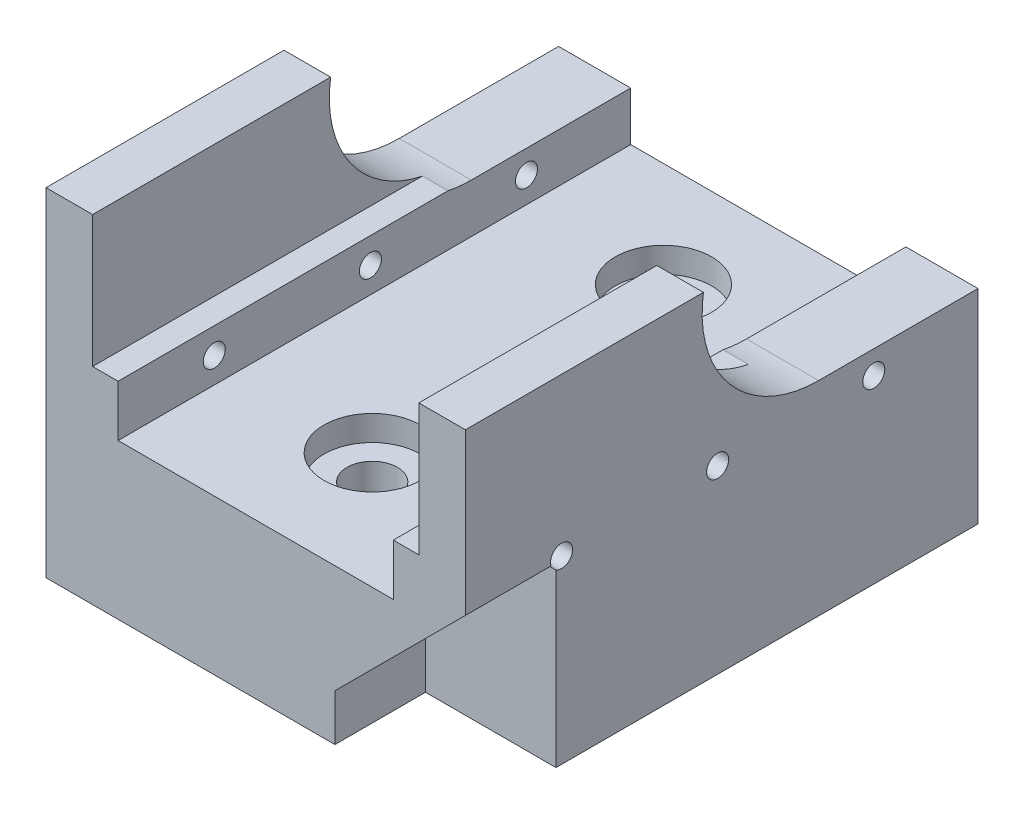
SolidWorks part; units mm, degrees
material "PLA"
ref_plane "Front Plane" through (0, 0, 0) normal (0, 0, 1) x (1, 0, 0)
ref_plane "Top Plane" through (0, 0, 0) normal (0, 1, 0) x (1, 0, 0)
ref_plane "Right Plane" through (0, 0, 0) normal (1, 0, 0) x (0, 0, -1)
sketch "Sketch1" plane through (0, 0, 0) normal (0, 1, 0) x (1, 0, 0)
  line L0 (-22.86, 30.48) -> (22.86, 30.48)
  line L6 (-22.86, 30.48) -> (-22.86, -30.48)
  line L8 (22.86, 30.48) -> (22.86, -30.48)
  line L9 (-22.86, -30.48) -> (22.86, -30.48)
  point P1 (-22.86, 0)
  point P7 (22.86, 0)
  dimension "D3" = 30.48
  dimension "D2" = 45.72
  dimension "D1" = 60.96
  dimension "D4" = 22.86
extrude "Boss-Extrude1" add sketch "Sketch1" along normal blind 6.35
sketch "Sketch2" plane through (0, 6.35, 0) normal (0, 1, 0) x (1, 0, 0)
  line L9 (-22.86, -30.48) -> (22.86, -30.48) construction
  line L10 (-22.86, 30.48) -> (-15, 30.48)
  line L11 (-22.86, 30.48) -> (-22.86, -30.48)
  line L12 (-22.86, -30.48) -> (-15, -30.48)
  line L13 (-15, 30.48) -> (-15, -30.48)
  line L14 (22.86, 30.48) -> (-22.86, 30.48) construction
  line L15 (15, 30.48) -> (22.86, 30.48)
  line L16 (15, 30.48) -> (15, -30.48)
  line L17 (15, -30.48) -> (22.86, -30.48)
  line L18 (22.86, 30.48) -> (22.86, -30.48)
  dimension "D1" = 7.86
  dimension "D2" = 7.86
extrude "Boss-Extrude2" add sketch "Sketch2" along normal blind 20.955
hole_wizard "M2 Clearance Hole2" positions "Sketch6" profile "Sketch7" hole size "M2" standard "ANSI Metric"
sketch "Sketch6" plane through (22.86, 0, 0) normal (1, 0, 0) x (0, 0, -1)
  line L0 (-30.48, 27.305) -> (-30.48, 0) construction
  line L1 (-30.48, 0) -> (30.48, 0) construction
  point P0 (-14.9172, 10.16)
  dimension "D1" = 15.5628
  dimension "D2" = 10.16
sketch "Sketch7" plane through (22.86, 10.16, 14.9172) normal (0, 1, 0) x (0, 0, -1)
  line L0 (0, 0) -> (0, 46.441)
  line L1 (0, 46.441) -> (1.2, 45.72)
  line L2 (1.2, 45.72) -> (1.2, 0)
  line L5 (1.2, 0) -> (0, 0)
  line L10 (0, 46.441) -> (-1.2, 45.72) construction
  line L11 (0, -6.35) -> (0, 107.95) construction
  dimension "Hole Dia." = 2.4
  dimension "Hole Depth" = 45.72
  dimension "Drill Angle" = 118
pattern_linear "LPattern1" count 3 spacing 17.018 along (0, 0, -1) of "M2 Clearance Hole2"
extrude "Boss-Extrude3" add sketch "Sketch1<3>" against normal blind 2.54
sketch "Sketch1<3>" plane through (0, 0, 0) normal (0, 1, 0) x (1, 0, 0) same geometry as "Sketch1"
sketch "Sketch8" plane through (-22.86, 0, 0) normal (-1, 0, 0) x (0, 0, 1)
  line L0 (-30.48, 27.305) -> (-30.48, -2.54) construction
  line L1 (-30.48, -2.54) -> (-14.605, -2.54)
  line L2 (-30.48, -2.54) -> (-30.48, 3.81)
  line L3 (-30.48, 3.81) -> (-14.605, 3.81)
  line L4 (-14.605, -2.54) -> (-14.605, 3.81)
  line L5 (-30.48, -2.54) -> (30.48, -2.54) construction
  dimension "D1" = 15.875
  dimension "D2" = 6.35
sketch "Sketch11" plane through (15, 0, 0) normal (-1, 0, 0) x (0, 0, 1)
  line L0 (30.48, 27.305) -> (30.48, 6.35) construction
  line L1 (-30.48, 27.305) -> (30.48, 27.305)
  line L2 (-30.48, 27.305) -> (-30.48, 12.96)
  line L3 (-30.48, 12.96) -> (30.48, 12.96)
  line L4 (30.48, 27.305) -> (30.48, 12.96)
  dimension "D1" = 14.345
extrude "Cut-Extrude1" cut sketch "Sketch11" against normal mid plane 35.56 from surface starting at plane "Right Plane"
sketch "Sketch12" plane through (22.86, 0, 0) normal (1, 0, 0) x (0, 0, -1)
  line L0 (30.48, 27.305) -> (30.48, -2.54) construction
  line L1 (13.105, 12.7) -> (30.48, 12.7)
  line L2 (30.48, 12.7) -> (30.48, 27.305)
  line L3 (30.48, 27.305) -> (25.6613, 27.305)
  line L5 (-30.48, 27.305) -> (30.48, 27.305) construction
  arc A0 (25.6613, 27.305) -> (13.105, 12.7) centre (13.105, 25.4) ccw
  dimension "D3" = 25.4
  dimension "D1" = 17.375
  dimension "D2" = 1.905
extrude "Cut-Extrude2" cut sketch "Sketch12" against normal through all
fillet "Fillet3" [suppressed] radius 0.762
sketch "Sketch17" plane through (0, -2.54, 0) normal (0, -1, 0) x (1, 0, 0)
  line L0 (-22.86, 30.48) -> (22.86, 30.48) construction
  line L1 (-22.86, 30.48) -> (22.86, 30.48)
  line L2 (-22.86, 30.48) -> (-22.86, -30.48)
  line L3 (-22.86, -30.48) -> (22.86, -30.48)
  line L4 (22.86, 30.48) -> (22.86, -30.48)
  line L5 (22.86, -30.48) -> (-22.86, -30.48) construction
  line L6 (22.86, 30.48) -> (22.86, -30.48) construction
  line L7 (-22.86, -30.48) -> (-22.86, 30.48) construction
extrude "Boss-Extrude4" add sketch "Sketch17" along normal blind 6.985
fillet "Fillet5" [suppressed] radius 0.762
sketch "Sketch19" plane through (0, 6.35, 0) normal (0, 1, 0) x (1, 0, 0)
  line L0 (15, 30.48) -> (15, -30.48) construction
  line L1 (-15, -30.48) -> (15, -30.48)
  line L2 (-15, -30.48) -> (-15, 30.48)
  line L3 (-15, 30.48) -> (15, 30.48)
  line L4 (15, -30.48) -> (15, 30.48)
  line L5 (15, 30.48) -> (-15, 30.48) construction
extrude "Boss-Extrude5" add sketch "Sketch19" along normal blind 1.01
hole_wizard "CBORE for M5 SBHCS2" positions "Sketch20" profile "Sketch21" counterbore size "M5" standard "ANSI Metric" end condition through all
sketch "Sketch20" plane through (0, 7.36, 0) normal (0, 1, 0) x (1, 0, 0)
  point P2 (0, -12.7)
  point P5 (0, 19.05)
  dimension "D1" = 31.75
  dimension "D2" = 12.7
sketch "Sketch21" plane through (0, 7.36, 12.7) normal (1, 0, 0) x (0, 0, 1)
  line L0 (0, 0) -> (0, 16.885)
  line L1 (0, 16.885) -> (2.75, 16.885)
  line L3 (2.75, 16.885) -> (2.75, 2.75)
  line L4 (2.75, 2.75) -> (5.25, 2.75)
  line L5 (5.25, 2.75) -> (5.25, 0)
  line L7 (5.25, 0) -> (0, 0)
  line L11 (0, -6.35) -> (0, 107.95) construction
  dimension "Thru Hole Dia." = 5.5
  dimension "Thru Hole Depth" = 16.885
  dimension "C'Bore Dia." = 10.5
  dimension "C'Bore Depth" = 2.75
fillet "Fillet6" [suppressed] radius 0.762
sketch "Sketch24" plane through (31.5712, -12.7, -14.6188) normal (0, 1, 0) x (0, 0, -1)
  line L0 (-45.0988, 8.7112) -> (-14.0701, 8.7112) construction
  line L1 (-45.0988, 54.4312) -> (-40.0188, 54.4312)
  line L2 (-45.0988, 54.4312) -> (-45.0988, 8.7112)
  line L3 (-45.0988, 8.7112) -> (-40.0188, 8.7112)
  line L4 (-40.0188, 54.4312) -> (-40.0188, 8.7112)
  dimension "D1" = 5.08
extrude "Cut-Extrude3" cut sketch "Sketch24" against normal through all both and the other way through all
sketch "Sketch25" plane through (0, 0, 25.4) normal (0, 0, 1) x (1, 0, 0)
  line L0 (8.636, -9.525) -> (8.636, -4.445)
  line L1 (22.86, -9.525) -> (-22.86, -9.525) construction
  line L2 (8.636, -4.445) -> (22.86, 9.779)
  line L3 (22.86, 27.305) -> (22.86, -9.525) construction
  line L4 (8.636, -9.525) -> (22.86, -9.525)
  line L5 (22.86, -9.525) -> (22.86, 9.779)
  dimension "D1" = 5.08
  dimension "D2" = 135
  dimension "D3" = 14.224
extrude "Cut-Extrude4" cut sketch "Sketch25" against normal blind 9.874
